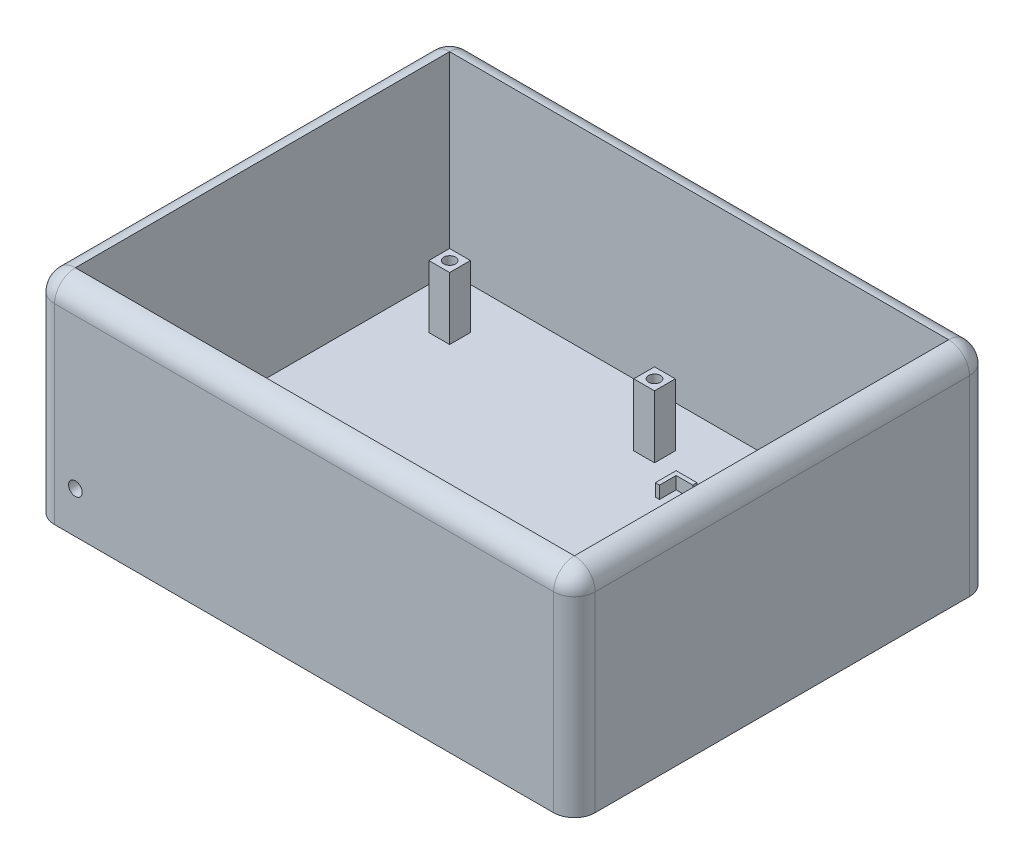
SolidWorks part; units mm, degrees
ref_plane "Front Plane" through (0, 0, 0) normal (0, 0, 1) x (1, 0, 0)
ref_plane "Top Plane" through (0, 0, 0) normal (0, 1, 0) x (1, 0, 0)
ref_plane "Right Plane" through (0, 0, 0) normal (1, 0, 0) x (0, 0, -1)
sketch "Sketch1" plane through (0, 0, 0) normal (0, 1, 0) x (1, 0, 0)
  line L1 (-65, 50) -> (65, 50)
  line L2 (-65, 50) -> (-65, -50)
  line L3 (-65, -50) -> (65, -50)
  line L4 (65, 50) -> (65, -50)
  line L5 (-65, 50) -> (65, -50) construction
  line L6 (-65, -50) -> (65, 50) construction
  point P0 (0, 0)
  dimension "D1" = 130
  dimension "D2" = 100
extrude "Boss-Extrude1" add sketch "Sketch1" along normal blind 51
sketch "Sketch2" plane through (0, 51, 0) normal (0, 1, 0) x (1, 0, 0)
  line L0 (-65, 50) -> (-65, -50) construction
  line L1 (-60, -45) -> (60, -45)
  line L2 (-60, -45) -> (-60, 45)
  line L3 (-60, 45) -> (60, 45)
  line L4 (60, -45) -> (60, 45)
  line L5 (-60, -45) -> (60, 45) construction
  line L6 (-60, 45) -> (60, -45) construction
  line L7 (65, 50) -> (-65, 50) construction
  point P0 (0, 0)
  dimension "D1" = 5
  dimension "D2" = 5
extrude "Cut-Extrude1" cut sketch "Sketch2" against normal blind 46
fillet "Fillet2" radius 5 4 edges at (0, 51, -50) (65, 51, 0) (0, 51, 50) (-65, 51, 0)
fillet "Fillet4" radius 5 8 edges at (65, 23, -50) (-65, 23, -50) (65, 23, 50) (-65, 23, 50) (63.5355, 49.5355, -48.5355) (-63.5355, 49.5355, -48.5355) (63.5355, 49.5355, 48.5355) (-63.5355, 49.5355, 48.5355)
sketch "Sketch6" plane through (0, 5, 0) normal (0, 1, 0) x (1, 0, 0)
  line L0 (60, 45) -> (-60, 45) construction
  line L1 (-50, 35) -> (-45, 35)
  line L2 (-50, 35) -> (-50, 30)
  line L3 (-50, 30) -> (-45, 30)
  line L4 (-45, 35) -> (-45, 30)
  line L5 (-50, 35) -> (-45, 30) construction
  line L6 (-50, 30) -> (-45, 35) construction
  line L7 (-50, -29.03) -> (-45, -29.03)
  line L8 (-50, -29.03) -> (-50, -34.03)
  line L9 (-50, -34.03) -> (-45, -34.03)
  line L10 (-45, -29.03) -> (-45, -34.03)
  line L11 (-50, -29.03) -> (-45, -34.03) construction
  line L12 (-50, -34.03) -> (-45, -29.03) construction
  line L13 (-0.73, 35) -> (4.27, 35)
  line L14 (-0.73, 35) -> (-0.73, 30)
  line L15 (-0.73, 30) -> (4.27, 30)
  line L16 (4.27, 35) -> (4.27, 30)
  line L17 (-0.73, 35) -> (4.27, 30) construction
  line L18 (-0.73, 30) -> (4.27, 35) construction
  line L24 (-0.73, -29.03) -> (4.27, -29.03)
  line L25 (-60, 45) -> (-60, -45) construction
  line L26 (-0.73, -29.03) -> (-0.73, -34.03)
  line L27 (-0.73, -34.03) -> (4.27, -34.03)
  line L28 (4.27, -29.03) -> (4.27, -34.03)
  line L29 (-0.73, -29.03) -> (4.27, -34.03) construction
  line L30 (-0.73, -34.03) -> (4.27, -29.03) construction
  point P0 (-47.5, 32.5)
  point P5 (-47.5, -31.53)
  point P10 (1.77, 32.5)
  point P15 (1.77, -31.53)
  dimension "D1" = 5
  dimension "D2" = 5
  dimension "D3" = 5
  dimension "D4" = 5
  dimension "D5" = 44.27
  dimension "D6" = 59.03
  dimension "D7" = 10
  dimension "D8" = 10
extrude "Boss-Extrude2" add sketch "Sketch6" along normal blind 15
sketch "Sketch9" plane through (0, 5, 0) normal (0, 1, 0) x (1, 0, 0)
  line L0 (11.5, -14.03) -> (11.5, -19.03)
  line L1 (11.5, -19.03) -> (16.5, -19.03)
  line L2 (16.5, -19.03) -> (16.5, -18.03)
  line L3 (16.5, -18.03) -> (12.5, -18.03)
  line L4 (12.5, -18.03) -> (12.5, -14.03)
  line L5 (12.5, -14.03) -> (11.5, -14.03)
  line L6 (11.5, 27.97) -> (16.5, 27.97)
  line L7 (16.5, 27.97) -> (16.5, 26.97)
  line L8 (16.5, 26.97) -> (12.5, 26.97)
  line L9 (12.5, 26.97) -> (12.5, 22.97)
  line L10 (12.5, 22.97) -> (11.5, 22.97)
  line L11 (11.5, 22.97) -> (11.5, 27.97)
  line L12 (40, 27.97) -> (40, 22.97)
  line L13 (40, 22.97) -> (39, 22.97)
  line L14 (39, 22.97) -> (39, 26.97)
  line L15 (39, 26.97) -> (35, 26.97)
  line L16 (35, 26.97) -> (35, 27.97)
  line L17 (35, 27.97) -> (40, 27.97)
  line L18 (40, -19.03) -> (35, -19.03)
  line L19 (35, -19.03) -> (35, -18.03)
  line L20 (35, -18.03) -> (39, -18.03)
  line L21 (39, -18.03) -> (39, -14.03)
  line L22 (39, -14.03) -> (40, -14.03)
  line L23 (40, -14.03) -> (40, -19.03)
  line L24 (60, -45) -> (60, 45) construction
  line L25 (4.27, -29.03) -> (-0.73, -29.03) construction
  dimension "D1" = 5
  dimension "D2" = 1
  dimension "D3" = 5
  dimension "D4" = 1
  dimension "D5" = 1
  dimension "D6" = 5
  dimension "D7" = 1
  dimension "D8" = 5
  dimension "D9" = 1
  dimension "D10" = 5
  dimension "D11" = 5
  dimension "D12" = 1
  dimension "D13" = 5
  dimension "D14" = 5
  dimension "D15" = 1
  dimension "D16" = 1
  dimension "D17" = 45
  dimension "D18" = 26.5
  dimension "D19" = 20
  dimension "D20" = 10
extrude "Boss-Extrude3" add sketch "Sketch9" along normal blind 3
hole_wizard "#4 Clearance Hole2" positions "Sketch13" profile "Sketch14" hole size "#4" standard "ANSI Inch"
sketch "Sketch13" plane through (58.9654, 20, -19.1453) normal (0, 1, 0) x (1, 0, 0)
  point P0 (-106.4654, -50.6753)
  point P1 (-57.1954, -50.6753)
  point P2 (-57.1954, 13.3547)
  point P3 (-106.4654, 13.3547)
sketch "Sketch14" plane through (-47.5, 20, 31.53) normal (1, 0, 0) x (0, 0, 1)
  line L0 (0, 0) -> (0, 10)
  line L1 (0, 10) -> (1.4224, 10)
  line L2 (1.4224, 10) -> (1.4224, 0)
  line L5 (1.4224, 0) -> (0, 0)
  line L11 (0, -6.35) -> (0, 107.95) construction
  dimension "Thru Hole Dia." = 2.8448
  dimension "Thru Hole Depth" = 10
hole_wizard "CSK for #4 Flat Head Machine Screw (100)1" positions "Sketch25" profile "Sketch26" countersink size "#4" standard "ANSI Inch"
sketch "Sketch25" plane through (58.9654, 7.3812, 55) normal (0, 0, 1) x (1, 0, 0)
  point P0 (-113.9654, 2.6188)
  point P7 (-113.9654, 5.5688)
sketch "Sketch26" plane through (-55, 10, 55) normal (1, 0, 0) x (0, -1, 0)
  line L0 (0, 0) -> (0, 10.9806)
  line L1 (0, 10.9806) -> (1.6319, 10)
  line L2 (1.6319, 10) -> (1.6319, 1.0284)
  line L3 (1.6319, 1.0284) -> (2.8575, 0)
  line L4 (2.8575, 0) -> (0, 0)
  line L5 (-1.6319, 1.0284) -> (-2.8575, 0) construction
  line L6 (0, 10.9806) -> (-1.6319, 10) construction
  line L7 (0, -6.35) -> (0, 107.95) construction
  dimension "Hole Dia." = 3.2639
  dimension "Hole Depth" = 10
  dimension "Near C'Sink Dia." = 5.715
  dimension "Near C'Sink Angle" = 100
  dimension "Drill Angle" = 118
hole_wizard "CSK for #4 Flat Head Machine Screw (100)2" positions "Sketch27" profile "Sketch28" countersink size "#4" standard "ANSI Inch"
sketch "Sketch27" plane through (58.9654, 7.3812, -55) normal (0, 0, -1) x (-1, 0, 0)
  point P0 (3.9654, 2.6188)
  point P9 (-1.0346, 6.8662)
sketch "Sketch28" plane through (55, 10, -55) normal (1, 0, 0) x (0, 1, 0)
  line L0 (0, 0) -> (0, 10.9806)
  line L1 (0, 10.9806) -> (1.6319, 10)
  line L2 (1.6319, 10) -> (1.6319, 1.0284)
  line L3 (1.6319, 1.0284) -> (2.8575, 0)
  line L4 (2.8575, 0) -> (0, 0)
  line L5 (-1.6319, 1.0284) -> (-2.8575, 0) construction
  line L6 (0, 10.9806) -> (-1.6319, 10) construction
  line L7 (0, -6.35) -> (0, 107.95) construction
  dimension "Hole Dia." = 3.2639
  dimension "Hole Depth" = 10
  dimension "Near C'Sink Dia." = 5.715
  dimension "Near C'Sink Angle" = 100
  dimension "Drill Angle" = 118
